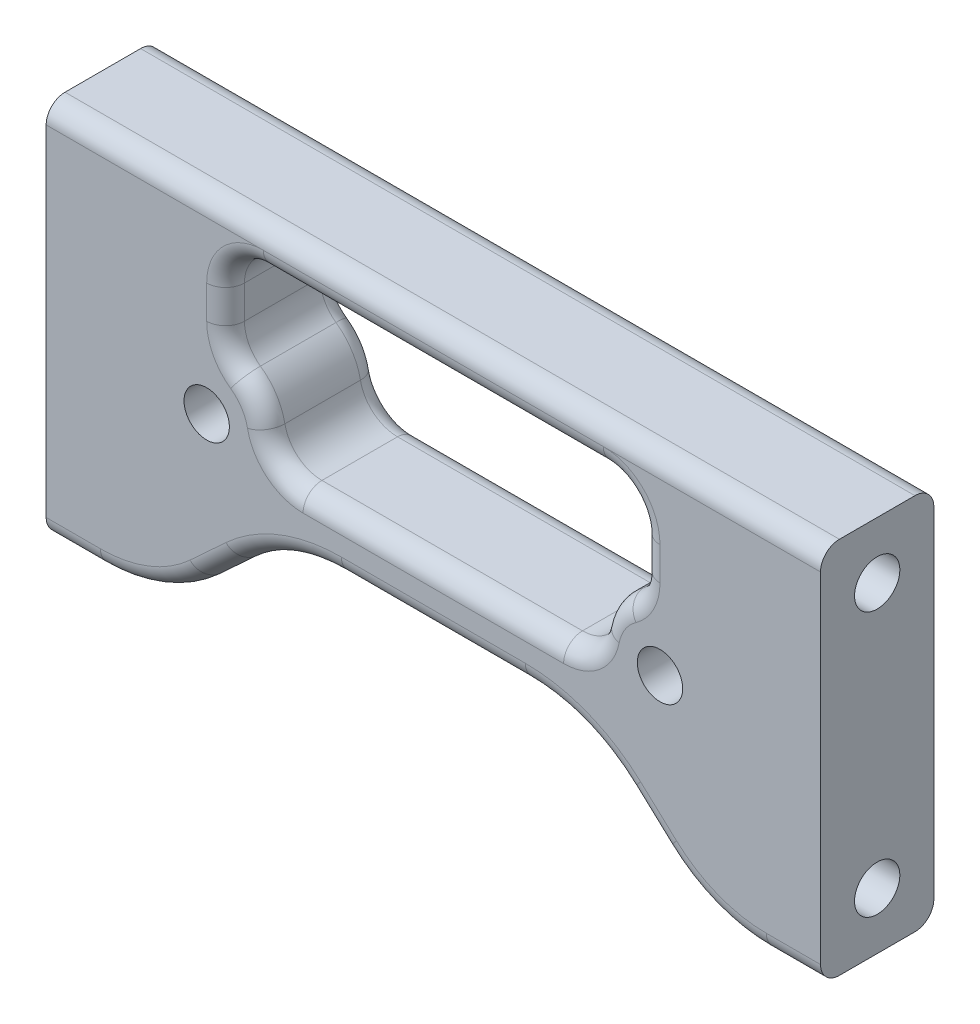
SolidWorks part; units mm, degrees
ref_plane "Front Plane" through (0, 0, 0) normal (0, 0, 1) x (1, 0, 0)
ref_plane "Top Plane" through (0, 0, 0) normal (0, 1, 0) x (1, 0, 0)
ref_plane "Right Plane" through (0, 0, 0) normal (1, 0, 0) x (0, 0, -1)
sketch "Sketch1" plane through (0, 0, 0) normal (0, 0, 1) x (1, 0, 0)
  line L1 (-32.5437, -15.875) -> (32.5438, -15.875)
  line L2 (-32.5437, -15.875) -> (-32.5437, 15.875)
  line L3 (-32.5437, 15.875) -> (32.5438, 15.875)
  line L4 (32.5438, -15.875) -> (32.5438, 15.875)
  line L5 (-32.5437, -15.875) -> (32.5438, 15.875) construction
  line L6 (-32.5437, 15.875) -> (32.5438, -15.875) construction
  point P0 (0, 0)
  dimension "D1" = 31.75
  dimension "D2" = 65.0875
extrude "Boss-Extrude1" add sketch "Sketch1" along normal mid plane 9.525
sketch "Sketch2" plane through (0, 0, 4.7625) normal (0, 0, 1) x (1, 0, 0)
  line L10 (-23.0187, -15.875) -> (-12.7, -6.35)
  line L11 (-32.5437, -15.875) -> (32.5438, -15.875) construction
  line L12 (-12.7, -6.35) -> (12.7, -6.35)
  line L13 (12.7, -6.35) -> (23.0187, -15.875)
  line L14 (23.0187, -15.875) -> (-23.0187, -15.875)
  point P6 (0, -6.35)
  point P7 (9.6592, -7.9131)
  dimension "D1" = 9.525
  dimension "D2" = 9.525
  dimension "D3" = 25.4
extrude "Cut-Extrude1" cut sketch "Sketch2" against normal through all
sketch "Sketch3" plane through (32.5438, 0, 0) normal (1, 0, 0) x (0, 0, -1)
  line L0 (0, -11.1125) -> (0, 11.1125) construction
  circle A0 centre (0, 11.1125) radius 1.905
  circle A1 centre (0, -11.1125) radius 1.905
  point P4 (0, 0)
  dimension "D1" = 3.81
  dimension "D2" = 22.225
extrude "Cut-Extrude2" cut sketch "Sketch3" against normal blind 12.7
mirror "Mirror2" about plane through (0, 0, 0) normal (1, 0, 0) of "Cut-Extrude2"
sketch "Sketch4" plane through (0, 0, -4.7625) normal (0, 0, -1) x (-1, 0, 0)
  line L0 (19.05, 0) -> (-19.05, 0) construction
  circle A0 centre (-19.05, 0) radius 1.905
  circle A1 centre (19.05, 0) radius 1.905
  point P4 (17.4608, 7.3187)
  point P5 (0, 0)
  dimension "D1" = 38.1
  dimension "D2" = 3.81
extrude "Cut-Extrude3" cut sketch "Sketch4" against normal through all
sketch "Sketch5" plane through (0, 0, -4.7625) normal (0, 0, -1) x (-1, 0, 0)
  line L0 (-14.2244, -1.5875) -> (14.2244, -1.5875)
  line L2 (17.4625, 4.8256) -> (17.4625, 12.7)
  line L3 (17.4625, 12.7) -> (-17.4625, 12.7)
  line L4 (-17.4625, 12.7) -> (-17.4625, 4.8256)
  line L6 (-12.7, -6.35) -> (12.7, -6.35) construction
  line L7 (-32.5438, 15.875) -> (32.5437, 15.875) construction
  arc A0 (-14.2244, -1.5875) -> (-17.4625, 4.8256) centre (-19.05, 0) ccw
  arc A1 (17.4625, 4.8256) -> (14.2244, -1.5875) centre (19.05, 0) ccw
  circle A2 centre (-19.05, 0) radius 1.905 construction
  point P11 (0, -1.5875)
  point P12 (0, 12.7)
  point P14 (16.5692, 12.2968)
  point P21 (16.6435, 12.7)
  point P22 (17.4625, 8.7628)
  dimension "D1" = 3.175
  dimension "D2" = 4.7625
  dimension "D3" = 3.175
  dimension "D4" = 34.925
extrude "Cut-Extrude4" cut sketch "Sketch5" against normal through all
fillet "Fillet3" radius 3.175 6 edges at (-17.4625, 12.7, 0) (-17.4625, 4.8256, 0) (17.4625, 4.8256, 0) (17.4625, 12.7, 0) (14.2244, -1.5875, 0) (-14.2244, -1.5875, 0)
fillet "Fillet6" radius 12.7 4 edges at (-23.0187, -15.875, 0) (-12.7, -6.35, 0) (23.0187, -15.875, 0) (12.7, -6.35, 0)
fillet "Fillet5" radius 1.5875 44 edges at (-17.1068, 5.2824, 4.7625) (17.1068, 5.2824, 4.7625) (-17.1068, 5.2824, -4.7625) (17.1068, 5.2824, -4.7625) (-16.5326, 11.7701, 4.7625) (16.5326, 11.7701, 4.7625) (-16.5326, 11.7701, -4.7625) (16.5326, 11.7701, -4.7625) (-14.786, 2.7613, 4.7625) (0, -1.5875, 4.7625) (14.786, 2.7613, 4.7625) (0, -1.5875, -4.7625) (-14.786, 2.7613, -4.7625) (14.786, 2.7613, -4.7625) (0, 12.7, 4.7625) (0, 12.7, -4.7625) (0, 15.875, 4.7625) (30.264, -15.875, 4.7625) (30.264, -15.875, -4.7625) (0, 15.875, -4.7625) (-30.264, -15.875, 4.7625) (-23.3597, -15.0031, 4.7625) (-17.8594, -11.1125, 4.7625) (-12.3591, -7.2219, 4.7625) (0, -6.35, 4.7625) (12.3591, -7.2219, 4.7625) (17.8594, -11.1125, 4.7625) (23.3597, -15.0031, 4.7625) (-30.264, -15.875, -4.7625) (-23.3597, -15.0031, -4.7625) (-17.8594, -11.1125, -4.7625) (-12.3591, -7.2219, -4.7625) (0, -6.35, -4.7625) (12.3591, -7.2219, -4.7625) (17.8594, -11.1125, -4.7625) (23.3597, -15.0031, -4.7625) (-17.4625, 8.1338, 4.7625) (-12.9668, -0.8639, 4.7625) (12.9668, -0.8639, 4.7625) (17.4625, 8.1338, 4.7625) (-17.4625, 8.1338, -4.7625) (-12.9668, -0.8639, -4.7625) (12.9668, -0.8639, -4.7625) (17.4625, 8.1338, -4.7625)
